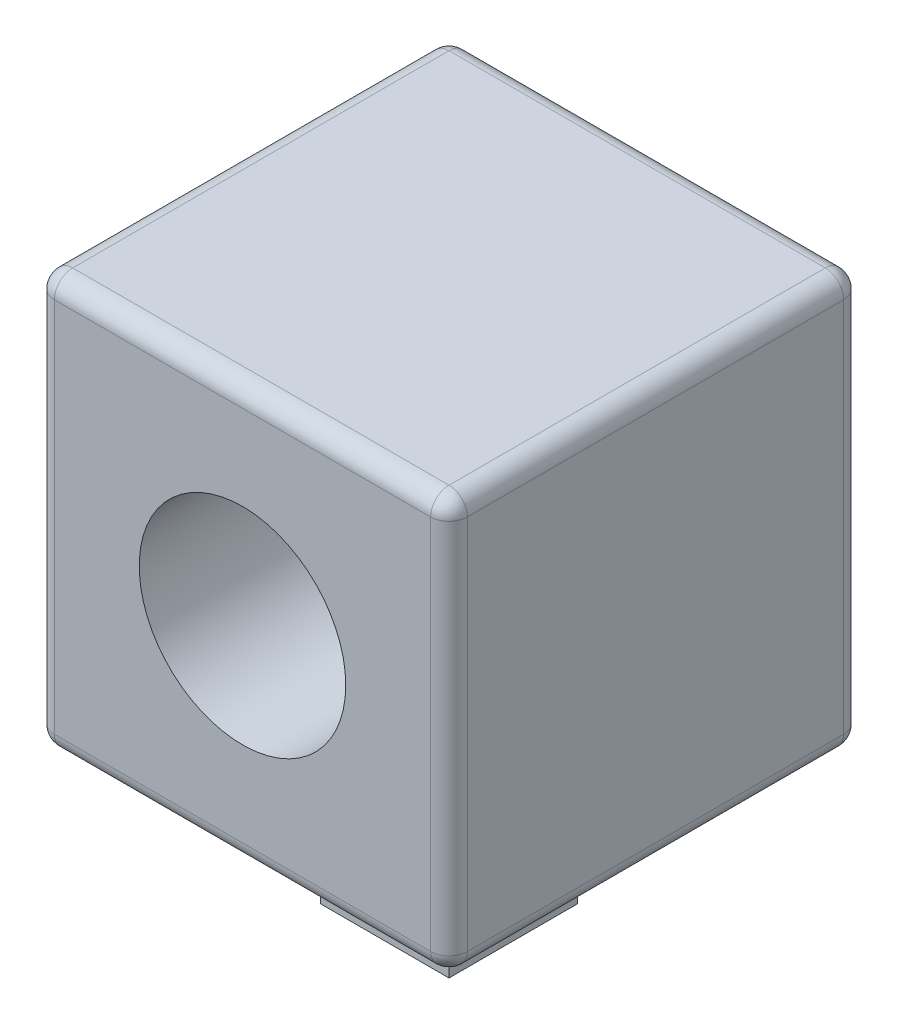
SolidWorks part; units mm, degrees
ref_plane "Front Plane" through (0, 0, 0) normal (0, 0, 1) x (1, 0, 0)
ref_plane "Top Plane" through (0, 0, 0) normal (0, 1, 0) x (1, 0, 0)
ref_plane "Right Plane" through (0, 0, 0) normal (1, 0, 0) x (0, 0, -1)
sketch "Sketch1" plane through (0, 0, 0) normal (0, 1, 0) x (1, 0, 0)
  line L1 (-8.89, -8.89) -> (8.89, -8.89)
  line L2 (-8.89, -8.89) -> (-8.89, 8.89)
  line L3 (-8.89, 8.89) -> (8.89, 8.89)
  line L4 (8.89, -8.89) -> (8.89, 8.89)
  line L5 (-8.89, -8.89) -> (8.89, 8.89) construction
  line L6 (-8.89, 8.89) -> (8.89, -8.89) construction
  point P0 (0, 0)
  dimension "D1" = 17.78
  dimension "D2" = 17.78
extrude "Boss-Extrude1" add sketch "Sketch1" along normal blind 12.7 and the other way blind 6.35
sketch "Sketch2" plane through (0, 12.7, 0) normal (0, 1, 0) x (1, 0, 0)
  line L1 (-28.575, -28.575) -> (28.575, -28.575)
  line L2 (-28.575, -28.575) -> (-28.575, 28.575)
  line L3 (-28.575, 28.575) -> (28.575, 28.575)
  line L4 (28.575, -28.575) -> (28.575, 28.575)
  line L5 (-28.575, -28.575) -> (28.575, 28.575) construction
  line L6 (-28.575, 28.575) -> (28.575, -28.575) construction
  point P0 (0, 0)
  dimension "D1" = 57.15
  dimension "D2" = 57.15
extrude "Boss-Extrude2" add sketch "Sketch2" along normal blind 57.15
sketch "Sketch3" plane through (0, 0, 28.575) normal (0, 0, 1) x (1, 0, 0)
  line L0 (-28.575, 69.85) -> (28.575, 69.85) construction
  line L1 (28.575, 69.85) -> (28.575, 12.7) construction
  circle A0 centre (0, 41.275) radius 14.2875
  dimension "D1" = 28.575
  dimension "D2" = 28.575
  dimension "D3" = 28.575
extrude "Cut-Extrude1" cut sketch "Sketch3" against normal through all
fillet "Fillet1" radius 2.54 12 edges at (28.575, 69.85, 0) (28.575, 12.7, 0) (-28.575, 69.85, 0) (-28.575, 12.7, 0) (28.575, 41.275, -28.575) (0, 69.85, -28.575) (-28.575, 41.275, -28.575) (0, 12.7, -28.575) (-28.575, 41.275, 28.575) (0, 69.85, 28.575) (28.575, 41.275, 28.575) (0, 12.7, 28.575)
